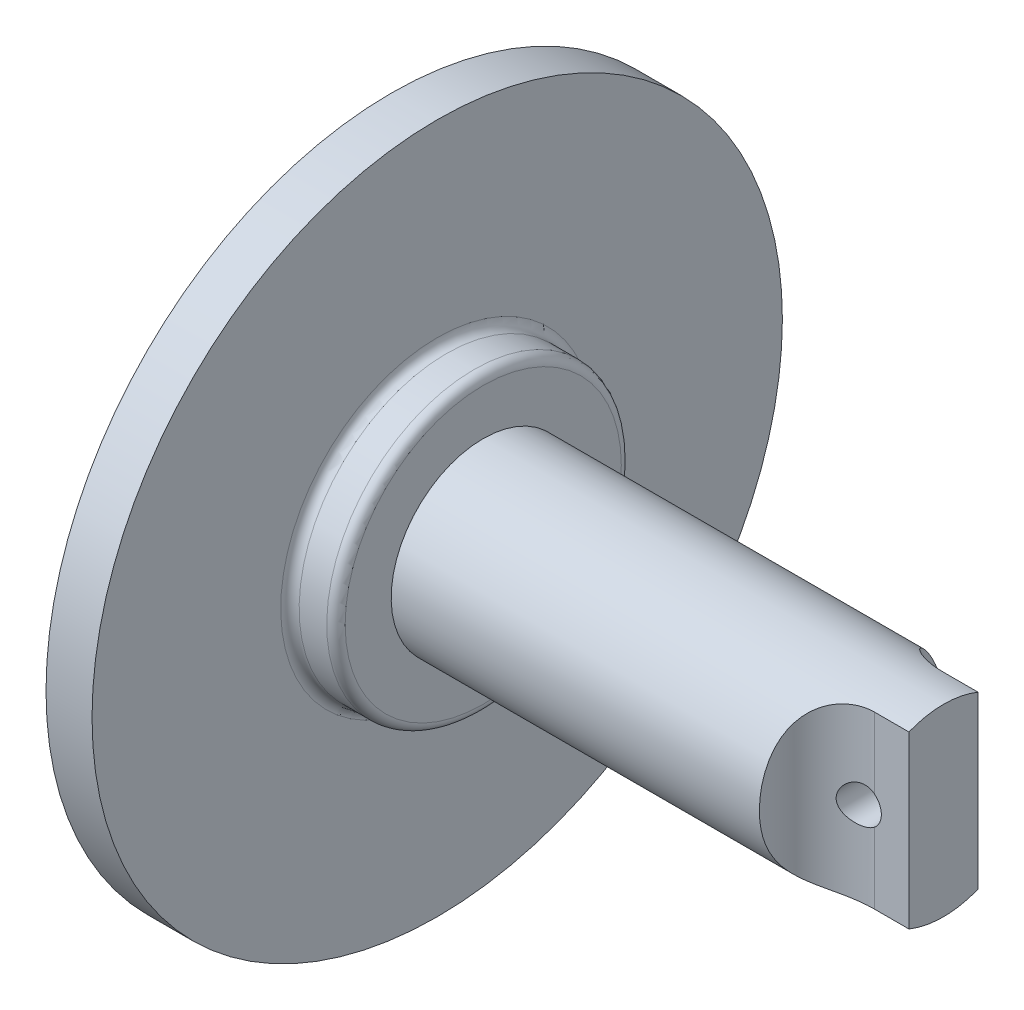
SolidWorks part; units mm, degrees
material "Cast Alloy Steel"
ref_plane "Front Plane" through (0, 0, 0) normal (0, 0, 1) x (1, 0, 0)
ref_plane "Top Plane" through (0, 0, 0) normal (0, 1, 0) x (1, 0, 0)
ref_plane "Right Plane" through (0, 0, 0) normal (1, 0, 0) x (0, 0, -1)
sketch "Sketch1" plane through (0, 0, 0) normal (0, 0, 1) x (1, 0, 0)
  line L0 (0, 0) -> (0, 75)
  line L1 (0, 75) -> (10, 75)
  line L2 (10, 75) -> (10, 34)
  line L3 (10, 0) -> (0, 0)
  line L4 (12, 32) -> (18, 32)
  line L5 (120, 0) -> (120, 20)
  line L6 (120, 0) -> (10, 0)
  line L7 (20, 30) -> (20, 20)
  line L8 (20, 20) -> (120, 20)
  arc A0 (20, 30) -> (18, 32) centre (18, 30) ccw
  arc A1 (12, 32) -> (10, 34) centre (12, 34) cw
  point P12 (20, 32)
  point P15 (10, 32)
  dimension "D6" = 2
  dimension "D1" = 10
  dimension "D2" = 75
  dimension "D3" = 10
  dimension "D4" = 20
  dimension "D5" = 100
  dimension "D7" = 10
revolve "Revolve1" add sketch "Sketch1" angle 360 about L6
sketch "Sketch2" plane through (120, 0, 0) normal (1, 0, 0) x (0, 0, -1)
  line L1 (-7.5, 18.5405) -> (-7.5, -18.5405)
  line L2 (7.5, 18.5405) -> (7.5, -18.5405)
  arc A0 (7.5, -18.5405) -> (7.5, 18.5405) centre (0, 0) ccw
  arc A1 (-7.5, 18.5405) -> (-7.5, -18.5405) centre (0, 0) ccw
extrude "Cut-Extrude1" cut sketch "Sketch2" against normal blind 20
fillet "Fillet1" radius 12.5 2 edges at (100, 0, -7.5) (100, 0, 7.5)
sketch "Sketch3" plane through (0, 0, 7.5) normal (0, 0, 1) x (1, 0, 0)
  line L0 (120, -18.5405) -> (120, 18.5405) construction
  circle A0 centre (110, 0) radius 4
  dimension "D2" = 8
  dimension "D1" = 10
extrude "Cut-Extrude2" cut sketch "Sketch3" against normal through all and the other way through all
